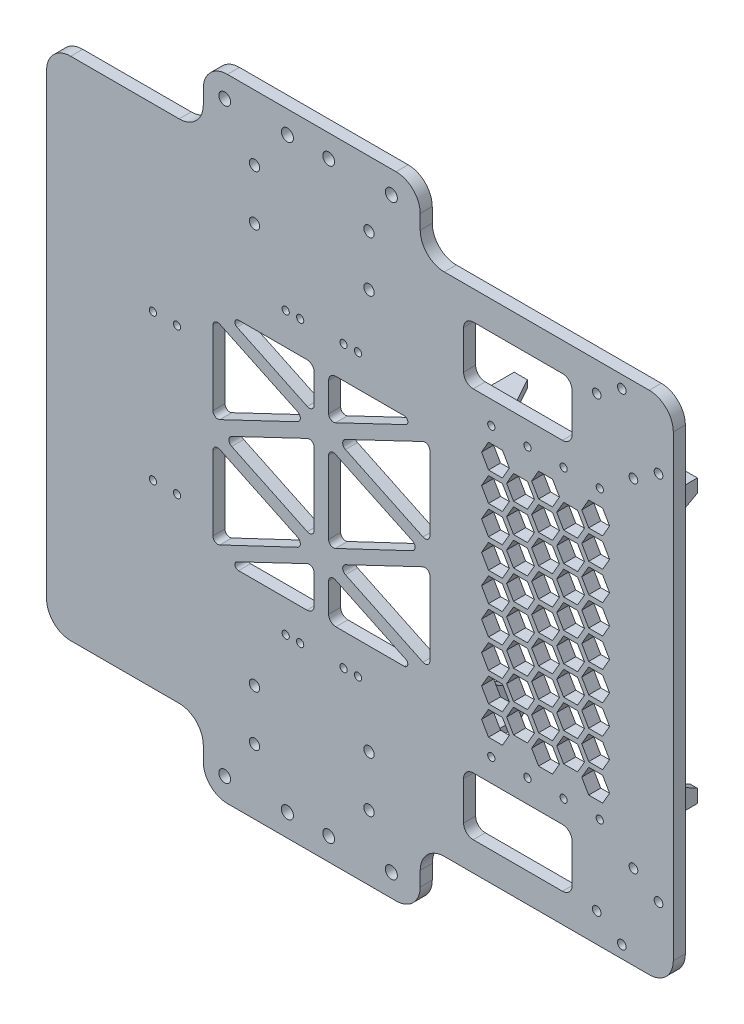
SolidWorks part; units mm, degrees
ref_plane "前视基准面" through (0, 0, 0) normal (0, 0, 1) x (1, 0, 0)
ref_plane "上视基准面" through (0, 0, 0) normal (0, 1, 0) x (1, 0, 0)
ref_plane "右视基准面" through (0, 0, 0) normal (1, 0, 0) x (0, 0, -1)
sketch "草图1" plane through (0, 0, 0) normal (0, 0, 1) x (1, 0, 0)
  line L2 (-130, 95) -> (-130, -95)
  line L3 (-120, -105) -> (-75, -105)
  line L4 (130, 95) -> (130, -95)
  line L5 (126.7518, 102.3765) -> (130, 105) construction
  line L6 (-130, -105) -> (-126.7518, -102.3765) construction
  line L9 (-65, -115) -> (-65, -121)
  line L10 (-55, -131) -> (15, -131)
  line L11 (25, -121) -> (25, -115)
  line L13 (35, -105) -> (120, -105)
  line L14 (126.7518, -102.3765) -> (130, -105) construction
  line L15 (-130, 105) -> (-126.7518, 102.3765) construction
  line L16 (-130, 0) -> (130, 0) construction
  line L17 (35, 105) -> (120, 105)
  line L18 (25, 121) -> (25, 115)
  line L19 (-55, 131) -> (15, 131)
  line L20 (-65, 115) -> (-65, 121)
  line L21 (-120, 105) -> (-75, 105)
  arc A1 (-120, -105) -> (-130, -95) centre (-120, -95) cw
  arc A3 (120, -105) -> (130, -95) centre (120, -95) ccw
  arc A8 (-65, -115) -> (-75, -105) centre (-75, -115) ccw
  arc A9 (25, -115) -> (35, -105) centre (35, -115) cw
  arc A10 (-55, -131) -> (-65, -121) centre (-55, -121) cw
  arc A11 (15, -131) -> (25, -121) centre (15, -121) ccw
  arc A12 (15, 131) -> (25, 121) centre (15, 121) cw
  arc A13 (-55, 131) -> (-65, 121) centre (-55, 121) ccw
  arc A14 (25, 115) -> (35, 105) centre (35, 115) ccw
  arc A15 (-65, 115) -> (-75, 105) centre (-75, 115) cw
  arc A16 (120, 105) -> (130, 95) centre (120, 95) cw
  arc A17 (-120, 105) -> (-130, 95) centre (-120, 95) ccw
  point P0 (0, 0)
  point P40 (25, -105)
  point P45 (25, 105)
  dimension "D2" = 10
  dimension "D3" = 65
  dimension "D4" = 10
  dimension "D5" = 105
  dimension "D7" = 10
  dimension "D8" = 10
  dimension "D10" = 10
  dimension "D12" = 10
  dimension "D13" = 105
  dimension "D18" = 90
  dimension "D19" = 6
extrude "凸台-拉伸1" add sketch "草图1" along normal blind 5
sketch "草图4" plane through (0, 0, 0) normal (0, 0, -1) x (-1, 0, 0)
  line L0 (-39, -47.5) -> (-39, -58.5)
  line L1 (-39, -58.5) -> (-50, -58.5)
  line L2 (-50, -58.5) -> (-50, -55.5)
  line L3 (-50, -55.5) -> (-42, -55.5)
  line L4 (-42, -55.5) -> (-42, -47.5)
  line L5 (-42, -47.5) -> (-39, -47.5)
  line L6 (-130, 0) -> (-25.5592, 0) construction
  line L7 (-130, -95) -> (-130, 95) construction
  line L10 (-130, -95) -> (-130, 95) construction
  dimension "D1" = 11
  dimension "D2" = 11
  dimension "D3" = 3
  dimension "D4" = 3
  dimension "D5" = 80
  dimension "D7" = 55.5
extrude "凸台-拉伸2" add sketch "草图4" along normal blind 20
sketch "草图5" plane through (0, -58.5, 0) normal (0, -1, 0) x (1, 0, 0)
  line L0 (50, -10) -> (44.5, -20)
  line L1 (50, -20) -> (50, 0) construction
  line L2 (50, -20) -> (39, -20) construction
  line L3 (44.5, -20) -> (50, -20)
  line L4 (50, -20) -> (50, -10)
  dimension "D1" = 10
  dimension "D2" = 5.5
extrude "切除-拉伸3" cut sketch "草图5" against normal blind 10
sketch "草图6" plane through (39, 0, 0) normal (-1, 0, 0) x (0, 0, 1)
  line L0 (-20, -53) -> (-10, -47.5)
  line L1 (-20, -58.5) -> (-20, -47.5) construction
  line L2 (-20, -47.5) -> (0, -47.5) construction
  line L3 (-10, -47.5) -> (-20, -47.5)
  line L4 (-20, -47.5) -> (-20, -53)
  dimension "D1" = 10
  dimension "D2" = 5.5
extrude "切除-拉伸4" cut sketch "草图6" against normal blind 10
ref_plane "基准面2" through (77, 0, 0) normal (1, 0, 0) x (0, 0, -1)
mirror "镜向1" about plane through (77, 0, 0) normal (1, 0, 0) of "凸台-拉伸2", "切除-拉伸4", "切除-拉伸3"
mirror "镜向2" about plane through (0, 0, 0) normal (0, 1, 0) of "镜向1"
sketch "草图7" plane through (0, 0, 0) normal (0, 0, -1) x (-1, 0, 0)
  line L4 (-112, -55.5) -> (-104, -55.5) construction
  line L5 (-112, 47.5) -> (-112, 55.5) construction
  line L6 (-112, 55.5) -> (-104, 55.5) construction
  line L7 (-92.013, 36) -> (-94.8997, 41)
  line L8 (-94.8997, 41) -> (-100.6732, 41)
  line L9 (-100.6732, 41) -> (-103.56, 36)
  line L10 (-103.56, 36) -> (-100.6732, 31)
  line L11 (-100.6732, 31) -> (-94.8997, 31)
  line L12 (-94.8997, 31) -> (-92.013, 36)
  line L13 (-77.0019, 36) -> (-97.7865, 36) construction
  line L14 (-74.1151, 31) -> (-71.2284, 36)
  line L15 (-71.2284, 36) -> (-74.1151, 41)
  line L16 (-74.1151, 41) -> (-79.8886, 41)
  line L17 (-79.8886, 41) -> (-82.7754, 36)
  line L18 (-82.7754, 36) -> (-79.8886, 31)
  line L19 (-79.8886, 31) -> (-74.1151, 31)
  line L20 (-92.013, 24) -> (-94.8997, 29)
  line L21 (-93.1677, 30) -> (-90.2809, 25)
  line L22 (-90.2809, 25) -> (-84.5074, 25)
  line L23 (-84.5074, 25) -> (-81.6207, 30)
  line L24 (-81.6207, 30) -> (-84.5074, 35)
  line L25 (-84.5074, 35) -> (-90.2809, 35)
  line L26 (-90.2809, 35) -> (-93.1677, 30)
  line L27 (-84.5074, 37) -> (-81.6207, 42)
  line L28 (-81.6207, 42) -> (-84.5074, 47)
  line L29 (-84.5074, 47) -> (-90.2809, 47)
  line L30 (-90.2809, 47) -> (-93.1677, 42)
  line L31 (-93.1677, 42) -> (-90.2809, 37)
  line L32 (-90.2809, 37) -> (-84.5074, 37)
  line L33 (-79.8886, 43) -> (-74.1151, 43)
  line L34 (-74.1151, 43) -> (-71.2284, 48)
  line L35 (-71.2284, 48) -> (-74.1151, 53)
  line L36 (-74.1151, 53) -> (-79.8886, 53)
  line L37 (-79.8886, 53) -> (-82.7754, 48)
  line L38 (-82.7754, 48) -> (-79.8886, 43)
  line L39 (-94.8997, 43) -> (-92.013, 48)
  line L40 (-92.013, 48) -> (-94.8997, 53)
  line L41 (-94.8997, 53) -> (-100.6732, 53)
  line L42 (-100.6732, 53) -> (-103.56, 48)
  line L43 (-103.56, 48) -> (-100.6732, 43)
  line L44 (-100.6732, 43) -> (-94.8997, 43)
  line L45 (-72.3831, 42) -> (-69.4963, 37)
  line L46 (-69.4963, 37) -> (-63.7228, 37)
  line L47 (-63.7228, 37) -> (-60.8361, 42)
  line L48 (-60.8361, 42) -> (-63.7228, 47)
  line L49 (-63.7228, 47) -> (-69.4963, 47)
  line L50 (-69.4963, 47) -> (-72.3831, 42)
  line L51 (-94.8997, 29) -> (-100.6732, 29)
  line L52 (-100.6732, 29) -> (-103.56, 24)
  line L53 (-103.56, 24) -> (-100.6732, 19)
  line L54 (-100.6732, 19) -> (-94.8997, 19)
  line L55 (-94.8997, 19) -> (-92.013, 24)
  line L56 (-93.1677, 18) -> (-90.2809, 13)
  line L57 (-90.2809, 13) -> (-84.5074, 13)
  line L58 (-84.5074, 13) -> (-81.6207, 18)
  line L59 (-81.6207, 18) -> (-84.5074, 23)
  line L60 (-84.5074, 23) -> (-90.2809, 23)
  line L61 (-90.2809, 23) -> (-93.1677, 18)
  line L62 (-74.1151, 19) -> (-71.2284, 24)
  line L63 (-71.2284, 24) -> (-74.1151, 29)
  line L64 (-74.1151, 29) -> (-79.8886, 29)
  line L65 (-79.8886, 29) -> (-82.7754, 24)
  line L66 (-82.7754, 24) -> (-79.8886, 19)
  line L67 (-79.8886, 19) -> (-74.1151, 19)
  line L68 (-72.3831, 30) -> (-69.4963, 25)
  line L69 (-69.4963, 25) -> (-63.7228, 25)
  line L70 (-63.7228, 25) -> (-60.8361, 30)
  line L71 (-60.8361, 30) -> (-63.7228, 35)
  line L72 (-63.7228, 35) -> (-69.4963, 35)
  line L73 (-69.4963, 35) -> (-72.3831, 30)
  line L74 (-92.013, 12) -> (-94.8997, 17)
  line L75 (-94.8997, 17) -> (-100.6732, 17)
  line L76 (-100.6732, 17) -> (-103.56, 12)
  line L77 (-103.56, 12) -> (-100.6732, 7)
  line L78 (-100.6732, 7) -> (-94.8997, 7)
  line L79 (-94.8997, 7) -> (-92.013, 12)
  line L80 (-93.1677, 6) -> (-90.2809, 1)
  line L81 (-90.2809, 1) -> (-84.5074, 1)
  line L82 (-84.5074, 1) -> (-81.6207, 6)
  line L83 (-81.6207, 6) -> (-84.5074, 11)
  line L84 (-84.5074, 11) -> (-90.2809, 11)
  line L85 (-90.2809, 11) -> (-93.1677, 6)
  line L86 (-74.1151, 7) -> (-71.2284, 12)
  line L87 (-71.2284, 12) -> (-74.1151, 17)
  line L88 (-74.1151, 17) -> (-79.8886, 17)
  line L89 (-79.8886, 17) -> (-82.7754, 12)
  line L90 (-82.7754, 12) -> (-79.8886, 7)
  line L91 (-79.8886, 7) -> (-74.1151, 7)
  line L92 (-72.3831, 18) -> (-69.4963, 13)
  line L93 (-69.4963, 13) -> (-63.7228, 13)
  line L94 (-63.7228, 13) -> (-60.8361, 18)
  line L95 (-60.8361, 18) -> (-63.7228, 23)
  line L96 (-63.7228, 23) -> (-69.4963, 23)
  line L97 (-69.4963, 23) -> (-72.3831, 18)
  line L98 (-92.013, 0) -> (-94.8997, 5)
  line L99 (-94.8997, 5) -> (-100.6732, 5)
  line L100 (-100.6732, 5) -> (-103.56, 0)
  line L101 (-103.56, 0) -> (-100.6732, -5)
  line L102 (-100.6732, -5) -> (-94.8997, -5)
  line L103 (-94.8997, -5) -> (-92.013, 0)
  line L104 (-93.1677, -6) -> (-90.2809, -11)
  line L105 (-90.2809, -11) -> (-84.5074, -11)
  line L106 (-84.5074, -11) -> (-81.6207, -6)
  line L107 (-81.6207, -6) -> (-84.5074, -1)
  line L108 (-84.5074, -1) -> (-90.2809, -1)
  line L109 (-90.2809, -1) -> (-93.1677, -6)
  line L110 (-74.1151, -5) -> (-71.2284, 0)
  line L111 (-71.2284, 0) -> (-74.1151, 5)
  line L112 (-74.1151, 5) -> (-79.8886, 5)
  line L113 (-79.8886, 5) -> (-82.7754, 0)
  line L114 (-82.7754, 0) -> (-79.8886, -5)
  line L115 (-79.8886, -5) -> (-74.1151, -5)
  line L116 (-72.3831, 6) -> (-69.4963, 1)
  line L117 (-69.4963, 1) -> (-63.7228, 1)
  line L118 (-63.7228, 1) -> (-60.8361, 6)
  line L119 (-60.8361, 6) -> (-63.7228, 11)
  line L120 (-63.7228, 11) -> (-69.4963, 11)
  line L121 (-69.4963, 11) -> (-72.3831, 6)
  line L122 (-92.013, -12) -> (-94.8997, -7)
  line L123 (-94.8997, -7) -> (-100.6732, -7)
  line L124 (-100.6732, -7) -> (-103.56, -12)
  line L125 (-103.56, -12) -> (-100.6732, -17)
  line L126 (-100.6732, -17) -> (-94.8997, -17)
  line L127 (-94.8997, -17) -> (-92.013, -12)
  line L128 (-93.1677, -18) -> (-90.2809, -23)
  line L129 (-90.2809, -23) -> (-84.5074, -23)
  line L130 (-84.5074, -23) -> (-81.6207, -18)
  line L131 (-81.6207, -18) -> (-84.5074, -13)
  line L132 (-84.5074, -13) -> (-90.2809, -13)
  line L133 (-90.2809, -13) -> (-93.1677, -18)
  line L134 (-74.1151, -17) -> (-71.2284, -12)
  line L135 (-71.2284, -12) -> (-74.1151, -7)
  line L136 (-74.1151, -7) -> (-79.8886, -7)
  line L137 (-79.8886, -7) -> (-82.7754, -12)
  line L138 (-82.7754, -12) -> (-79.8886, -17)
  line L139 (-79.8886, -17) -> (-74.1151, -17)
  line L140 (-72.3831, -6) -> (-69.4963, -11)
  line L141 (-69.4963, -11) -> (-63.7228, -11)
  line L142 (-63.7228, -11) -> (-60.8361, -6)
  line L143 (-60.8361, -6) -> (-63.7228, -1)
  line L144 (-63.7228, -1) -> (-69.4963, -1)
  line L145 (-69.4963, -1) -> (-72.3831, -6)
  line L146 (-92.013, -24) -> (-94.8997, -19)
  line L147 (-94.8997, -19) -> (-100.6732, -19)
  line L148 (-100.6732, -19) -> (-103.56, -24)
  line L149 (-103.56, -24) -> (-100.6732, -29)
  line L150 (-100.6732, -29) -> (-94.8997, -29)
  line L151 (-94.8997, -29) -> (-92.013, -24)
  line L152 (-93.1677, -30) -> (-90.2809, -35)
  line L153 (-90.2809, -35) -> (-84.5074, -35)
  line L154 (-84.5074, -35) -> (-81.6207, -30)
  line L155 (-81.6207, -30) -> (-84.5074, -25)
  line L156 (-84.5074, -25) -> (-90.2809, -25)
  line L157 (-90.2809, -25) -> (-93.1677, -30)
  line L158 (-74.1151, -29) -> (-71.2284, -24)
  line L159 (-71.2284, -24) -> (-74.1151, -19)
  line L160 (-74.1151, -19) -> (-79.8886, -19)
  line L161 (-79.8886, -19) -> (-82.7754, -24)
  line L162 (-82.7754, -24) -> (-79.8886, -29)
  line L163 (-79.8886, -29) -> (-74.1151, -29)
  line L164 (-72.3831, -18) -> (-69.4963, -23)
  line L165 (-69.4963, -23) -> (-63.7228, -23)
  line L166 (-63.7228, -23) -> (-60.8361, -18)
  line L167 (-60.8361, -18) -> (-63.7228, -13)
  line L168 (-63.7228, -13) -> (-69.4963, -13)
  line L169 (-69.4963, -13) -> (-72.3831, -18)
  line L170 (-92.013, -36) -> (-94.8997, -31)
  line L171 (-94.8997, -31) -> (-100.6732, -31)
  line L172 (-100.6732, -31) -> (-103.56, -36)
  line L173 (-103.56, -36) -> (-100.6732, -41)
  line L174 (-100.6732, -41) -> (-94.8997, -41)
  line L175 (-94.8997, -41) -> (-92.013, -36)
  line L176 (-93.1677, -42) -> (-90.2809, -47)
  line L177 (-90.2809, -47) -> (-84.5074, -47)
  line L178 (-84.5074, -47) -> (-81.6207, -42)
  line L179 (-81.6207, -42) -> (-84.5074, -37)
  line L180 (-84.5074, -37) -> (-90.2809, -37)
  line L181 (-90.2809, -37) -> (-93.1677, -42)
  line L182 (-74.1151, -41) -> (-71.2284, -36)
  line L183 (-71.2284, -36) -> (-74.1151, -31)
  line L184 (-74.1151, -31) -> (-79.8886, -31)
  line L185 (-79.8886, -31) -> (-82.7754, -36)
  line L186 (-82.7754, -36) -> (-79.8886, -41)
  line L187 (-79.8886, -41) -> (-74.1151, -41)
  line L188 (-72.3831, -30) -> (-69.4963, -35)
  line L189 (-69.4963, -35) -> (-63.7228, -35)
  line L190 (-63.7228, -35) -> (-60.8361, -30)
  line L191 (-60.8361, -30) -> (-63.7228, -25)
  line L192 (-63.7228, -25) -> (-69.4963, -25)
  line L193 (-69.4963, -25) -> (-72.3831, -30)
  line L194 (-92.013, -48) -> (-94.8997, -43)
  line L195 (-94.8997, -43) -> (-100.6732, -43)
  line L196 (-100.6732, -43) -> (-103.56, -48)
  line L197 (-103.56, -48) -> (-100.6732, -53)
  line L198 (-100.6732, -53) -> (-94.8997, -53)
  line L199 (-94.8997, -53) -> (-92.013, -48)
  line L206 (-74.1151, -53) -> (-71.2284, -48)
  line L207 (-71.2284, -48) -> (-74.1151, -43)
  line L208 (-74.1151, -43) -> (-79.8886, -43)
  line L209 (-79.8886, -43) -> (-82.7754, -48)
  line L210 (-82.7754, -48) -> (-79.8886, -53)
  line L211 (-79.8886, -53) -> (-74.1151, -53)
  line L212 (-72.3831, -42) -> (-69.4963, -47)
  line L213 (-69.4963, -47) -> (-63.7228, -47)
  line L214 (-63.7228, -47) -> (-60.8361, -42)
  line L215 (-60.8361, -42) -> (-63.7228, -37)
  line L216 (-63.7228, -37) -> (-69.4963, -37)
  line L217 (-69.4963, -37) -> (-72.3831, -42)
  line L218 (-61.9908, 36) -> (-59.104, 31)
  line L219 (-61.9908, 48) -> (-59.104, 43)
  line L220 (-59.104, 43) -> (-53.3305, 43)
  line L221 (-53.3305, 43) -> (-50.4438, 48)
  line L222 (-50.4438, 48) -> (-53.3305, 53)
  line L223 (-53.3305, 53) -> (-59.104, 53)
  line L224 (-59.104, 53) -> (-61.9908, 48)
  line L225 (-59.104, 31) -> (-53.3305, 31)
  line L226 (-53.3305, 31) -> (-50.4438, 36)
  line L227 (-50.4438, 36) -> (-53.3305, 41)
  line L228 (-53.3305, 41) -> (-59.104, 41)
  line L229 (-59.104, 41) -> (-61.9908, 36)
  line L230 (-61.9908, 24) -> (-59.104, 19)
  line L231 (-59.104, 19) -> (-53.3305, 19)
  line L232 (-53.3305, 19) -> (-50.4438, 24)
  line L233 (-50.4438, 24) -> (-53.3305, 29)
  line L234 (-53.3305, 29) -> (-59.104, 29)
  line L235 (-59.104, 29) -> (-61.9908, 24)
  line L236 (-61.9908, 12) -> (-59.104, 7)
  line L237 (-59.104, 7) -> (-53.3305, 7)
  line L238 (-53.3305, 7) -> (-50.4438, 12)
  line L239 (-50.4438, 12) -> (-53.3305, 17)
  line L240 (-53.3305, 17) -> (-59.104, 17)
  line L241 (-59.104, 17) -> (-61.9908, 12)
  line L242 (-61.9908, 0) -> (-59.104, -5)
  line L243 (-59.104, -5) -> (-53.3305, -5)
  line L244 (-53.3305, -5) -> (-50.4438, 0)
  line L245 (-50.4438, 0) -> (-53.3305, 5)
  line L246 (-53.3305, 5) -> (-59.104, 5)
  line L247 (-59.104, 5) -> (-61.9908, 0)
  line L248 (-61.9908, -12) -> (-59.104, -17)
  line L249 (-59.104, -17) -> (-53.3305, -17)
  line L250 (-53.3305, -17) -> (-50.4438, -12)
  line L251 (-50.4438, -12) -> (-53.3305, -7)
  line L252 (-53.3305, -7) -> (-59.104, -7)
  line L253 (-59.104, -7) -> (-61.9908, -12)
  line L254 (-61.9908, -24) -> (-59.104, -29)
  line L255 (-59.104, -29) -> (-53.3305, -29)
  line L256 (-53.3305, -29) -> (-50.4438, -24)
  line L257 (-50.4438, -24) -> (-53.3305, -19)
  line L258 (-53.3305, -19) -> (-59.104, -19)
  line L259 (-59.104, -19) -> (-61.9908, -24)
  line L260 (-61.9908, -36) -> (-59.104, -41)
  line L261 (-59.104, -41) -> (-53.3305, -41)
  line L262 (-53.3305, -41) -> (-50.4438, -36)
  line L263 (-50.4438, -36) -> (-53.3305, -31)
  line L264 (-53.3305, -31) -> (-59.104, -31)
  line L265 (-59.104, -31) -> (-61.9908, -36)
  line L266 (-61.9908, -48) -> (-59.104, -53)
  line L267 (-59.104, -53) -> (-53.3305, -53)
  line L268 (-53.3305, -53) -> (-50.4438, -48)
  line L269 (-50.4438, -48) -> (-53.3305, -43)
  line L270 (-53.3305, -43) -> (-59.104, -43)
  line L271 (-59.104, -43) -> (-61.9908, -48)
  line L272 (-93.1677, -54) -> (-90.2809, -59) [skipped]
  line L273 (-90.2809, -59) -> (-84.5074, -59) [skipped]
  line L274 (-84.5074, -59) -> (-81.6207, -54) [skipped]
  line L275 (-81.6207, -54) -> (-84.5074, -49) [skipped]
  line L276 (-84.5074, -49) -> (-90.2809, -49) [skipped]
  line L277 (-90.2809, -49) -> (-93.1677, -54) [skipped]
  circle A0 centre (-97.7865, 36) radius 5 construction
  circle A1 centre (-77.0019, 36) radius 5 construction
  circle A2 centre (-87.3942, 30) radius 5 construction
  circle A3 centre (-87.3942, 42) radius 5 construction
  circle A4 centre (-77.0019, 48) radius 5 construction
  circle A5 centre (-97.7865, 48) radius 5 construction
  circle A6 centre (-66.6096, 42) radius 5 construction
  circle A7 centre (-56.2173, 48) radius 5 construction
  point P4 (-87.3942, 37)
  dimension "D1" = 2
  dimension "D3" = 10
  dimension "D4" = 10
  dimension "D5" = 2
  dimension "D7" = 10
  dimension "D11" = 10
  dimension "D14" = 10
  dimension "D15" = 10
  dimension "D20" = 10
  dimension "D2" = 2
  dimension "D6" = 2
  dimension "D8" = 2
  dimension "D9" = 2
  dimension "D10" = 2
  dimension "D12" = 2
  dimension "D13" = 2
  dimension "D16" = 2
  dimension "D17" = 2
  dimension "D19" = 2
  dimension "D21" = 9
  dimension "D22" = 2.5
  dimension "D23" = 2.5
  dimension "D24" = 8.44
  dimension "D18" = 8
extrude "切除-拉伸5" cut sketch "草图7" against normal blind 5
sketch "草图8" plane through (0, 0, 0) normal (0, 0, -1) x (-1, 0, 0)
  line L0 (-75.3677, 120) -> (-75.3677, -120)
  line L1 (-100.0285, 77.2863) -> (-100.0285, -77.2863)
  line L2 (-100.0285, 77.2863) -> (-75.3677, 120)
  line L3 (-100.0285, -77.2863) -> (-75.3677, -120)
  line L4 (-37.1297, 0) -> (-146.8562, 0) construction
  dimension "D1" = 30
  dimension "D2" = 30
  dimension "D3" = 120
  dimension "D4" = 120
sketch "草图9" plane through (0, 0, 0) normal (0, 0, -1) x (-1, 0, 0)
  line L0 (148.8518, 0) -> (-37.1297, 0) construction
  line L1 (-29, 41) -> (-29, 4)
  line L2 (-25, -45) -> (13, -45)
  line L3 (61, -41) -> (61, -4)
  line L4 (57, 45) -> (19, 45)
  line L14 (-29, 41) -> (9.8049, 22.5)
  line L15 (57, 0) -> (19, -18.1163)
  line L16 (130, 95) -> (130, -95) construction
  line L17 (63, 93) -> (118, 93)
  line L18 (63, 93) -> (63, 66)
  line L19 (63, 66) -> (118, 66)
  line L20 (118, 93) -> (118, 66)
  line L21 (75, 105) -> (120, 105) construction
  line L22 (63, -66) -> (118, -66)
  line L23 (118, -93) -> (118, -66)
  line L24 (63, -93) -> (118, -93)
  line L25 (63, -93) -> (63, -66)
  line L26 (-120, 105) -> (-35, 105) construction
  line L27 (-43, 93) -> (-88, 93)
  line L28 (-43, 93) -> (-43, 69)
  line L29 (-43, 69) -> (-88, 69)
  line L30 (-88, 93) -> (-88, 69)
  line L31 (-130, -95) -> (-130, 95) construction
  line L32 (-43, -69) -> (-88, -69)
  line L33 (-88, -93) -> (-88, -69)
  line L34 (-43, -93) -> (-88, -93)
  line L35 (-43, -93) -> (-43, -69)
  line L36 (-25, 45) -> (13, 26.8837)
  line L37 (-25, -45) -> (13, -26.8837)
  line L38 (61, 41) -> (22.0746, 22.5575)
  line L39 (-25.5359, 0) -> (13, -18.258)
  line L40 (57, 45) -> (19, 26.8837)
  line L41 (57, -45) -> (19, -26.8837)
  line L42 (16, 61.4977) -> (16, -60.5731) construction
  line L43 (13, 45) -> (13, 26.8837)
  line L44 (19, 45) -> (19, 26.8837)
  line L45 (13, 18.258) -> (13, -18.258)
  line L46 (9.8049, 22.5) -> (-29, 4)
  line L47 (19, 18.1163) -> (57, 0)
  line L48 (22.0746, 22.5575) -> (61, 4)
  line L49 (13, 18.258) -> (-25.5359, 0)
  line L50 (19, 18.1163) -> (19, -18.1163)
  line L51 (22.0746, -22.5575) -> (61, -41)
  line L52 (9.8049, -22.5) -> (-29, -41)
  line L53 (9.8049, -22.5) -> (-29, -4)
  line L54 (22.0746, -22.5575) -> (61, -4)
  line L55 (13, -26.8837) -> (13, -45)
  line L56 (19, -26.8837) -> (19, -45)
  line L57 (13, 45) -> (-25, 45)
  line L58 (-29, -4) -> (-29, -41)
  line L59 (19, -45) -> (57, -45)
  line L60 (61, 4) -> (61, 41)
  line L61 (-44, 41) -> (-44, -37.8122) construction
  dimension "D1" = 45
  dimension "D2" = 45
  dimension "D3" = 15
  dimension "D4" = 90
  dimension "D5" = 1
  dimension "D7" = 12
  dimension "D8" = 12
  dimension "D9" = 27
  dimension "D10" = 55
  dimension "D11" = 12
  dimension "D12" = 45
  dimension "D13" = 42
  dimension "D14" = 24
  dimension "D21" = 4
  dimension "D22" = 4
  dimension "D23" = 4
  dimension "D24" = 4
  dimension "D26" = 4
  dimension "D27" = 3
  dimension "D28" = 45
extrude "切除-拉伸6" cut sketch "草图9" against normal blind 5 contours L27 L30 L29 L28 | L34 L35 L32 L33 | L4 L44 L40 | L48 L60 L38 | L47 L50 L15 | L54 L51 L3 | L56 L59 L41 | L55 L37 L2 | L53 L58 L52 | L45 L49 L39 | L46 L14 L1 | L43 L57 L36 | L57 L36 L43 region at (16.065, 22.5, 0) region at (-0.3333, -38.9612, 0) region at (-48.0249, -22.5192, 0) region at (-31.6667, 38.9612, 0) region at (-31.6667, 0, 0) region at (65.5, 81, 0) region at (65.5, -81, 0) region at (-0.3333, 38.9612, 0) region at (-48.0249, 22.5192, 0) region at (-0.1547, 0, 0) region at (-31.6667, -38.9612, 0) region at (16.065, -22.5, 0)
fillet "圆角1" radius 4 8 edges at (43, -93, 2.5) (88, -69, 2.5) (43, -69, 2.5) (88, -93, 2.5) (88, 69, 2.5) (43, 69, 2.5) (43, 93, 2.5) (88, 93, 2.5)
fillet "圆角2" radius 1.5 4 edges at (25, -45, 2.5) (-57, -45, 2.5) (25, 45, 2.5) (-57, 45, 2.5)
fillet "圆角3" radius 2 22 edges at (29, -4, 2.5) (29, 4, 2.5) (-13, -18.258, 2.5) (-61, -41, 2.5) (-61, 4, 2.5) (-13, -26.8837, 2.5) (-13, 18.258, 2.5) (-61, -4, 2.5) (-22.0746, -22.5575, 2.5) (25.5359, 0, 2.5) (-22.0746, 22.5575, 2.5) (-61, 41, 2.5) (-19, 26.8837, 2.5) (-19, -26.8837, 2.5) (-19, -18.1163, 2.5) (29, -41, 2.5) (29, 41, 2.5) (-57, 0, 2.5) (-9.8049, -22.5, 2.5) (-13, 26.8837, 2.5) (-9.8049, 22.5, 2.5) (-19, 18.1163, 2.5)
fillet "圆角4" radius 3 4 edges at (-13, -45, 2.5) (-13, 45, 2.5) (-19, -45, 2.5) (-19, 45, 2.5)
sketch "草图10" plane through (0, 0, 0) normal (0, 0, -1) x (-1, 0, 0)
  line L0 (-37.1297, 0) -> (-146.8562, 0) construction
  line L1 (-37.1297, 0) -> (-146.8562, 0) construction
  circle A0 centre (-123.8743, 76.9597) radius 1.8 construction
  circle A1 centre (-113.4687, 70.0334) radius 1.8 construction
  circle A2 centre (-108.6364, 99.852) radius 1.8 construction
  circle A3 centre (-98.2308, 92.9256) radius 1.8 construction
  circle A4 centre (-3.75, 104) radius 2.15 construction
  circle A5 centre (-3.75, 104) radius 2.15
  circle A6 centre (-3.75, -104) radius 2.15
  circle A11 centre (-13.0267, 121.679) radius 2.5 construction
  circle A12 centre (56.0941, 121.679) radius 2.45 construction
  circle A13 centre (30.0941, 121.679) radius 2.5 construction
  circle A14 centre (12.9733, 121.679) radius 2.45 construction
  circle A15 centre (-123.8743, 76.9597) radius 1.8
  circle A16 centre (-113.4687, 70.0334) radius 1.8
  circle A17 centre (-108.6364, 99.852) radius 1.8
  circle A18 centre (-98.2308, 92.9256) radius 1.8
  circle A26 centre (-13.0267, 121.679) radius 2.5
  circle A27 centre (56.0941, 121.679) radius 2.45
  circle A28 centre (30.0941, 121.679) radius 2.5
  circle A29 centre (12.9733, 121.679) radius 2.45
  circle A30 centre (12.9733, -121.679) radius 2.45
  circle A31 centre (30.0941, -121.679) radius 2.5
  circle A32 centre (56.0941, -121.679) radius 2.45
  circle A33 centre (-13.0267, -121.679) radius 2.5
  circle A41 centre (-98.2308, -92.9256) radius 1.8
  circle A42 centre (-108.6364, -99.852) radius 1.8
  circle A43 centre (-113.4687, -70.0334) radius 1.8
  circle A44 centre (-123.8743, -76.9597) radius 1.8
  circle A45 centre (-99.5, 59.5) radius 1.5 construction
  circle A46 centre (-84.5, 59.5) radius 1.5 construction
  circle A47 centre (-69.5, 59.5) radius 1.5 construction
  circle A48 centre (-54.5, 59.5) radius 1.5 construction
  circle A49 centre (0.8061, 58.25) radius 1.5 construction
  circle A50 centre (6.8061, 58.25) radius 1.5 construction
  circle A51 centre (24.8061, 58.25) radius 1.5 construction
  circle A52 centre (30.8061, 58.25) radius 1.5 construction
  circle A53 centre (-99.5, 59.5) radius 1.5
  circle A54 centre (-84.5, 59.5) radius 1.5
  circle A55 centre (-69.5, 59.5) radius 1.5
  circle A56 centre (-54.5, 59.5) radius 1.5
  circle A57 centre (0.8061, 58.25) radius 1.5
  circle A58 centre (6.8061, 58.25) radius 1.5
  circle A59 centre (24.8061, 58.25) radius 1.5
  circle A60 centre (30.8061, 58.25) radius 1.5
  circle A61 centre (30.8061, -58.25) radius 1.5
  circle A62 centre (24.8061, -58.25) radius 1.5
  circle A63 centre (6.8061, -58.25) radius 1.5
  circle A64 centre (0.8061, -58.25) radius 1.5
  circle A65 centre (-54.5, -59.5) radius 1.5
  circle A66 centre (-69.5, -59.5) radius 1.5
  circle A67 centre (-84.5, -59.5) radius 1.5
  circle A68 centre (-99.5, -59.5) radius 1.5
  circle A89 centre (75.897, 30.3) radius 1.5 construction
  circle A90 centre (85.897, 30.3) radius 1.5 construction
  circle A91 centre (75.897, 30.3) radius 1.5
  circle A92 centre (85.897, 30.3) radius 1.5
  circle A93 centre (85.897, -30.3) radius 1.5
  circle A94 centre (75.897, -30.3) radius 1.5
  circle A95 centre (43.75, 83) radius 2.15 construction
  circle A96 centre (43.75, 104) radius 2.15 construction
  circle A97 centre (-3.75, 83) radius 2.15 construction
  circle A99 centre (43.75, 83) radius 2.15
  circle A100 centre (43.75, 104) radius 2.15
  circle A101 centre (-3.75, 83) radius 2.15
  circle A104 centre (-3.75, -83) radius 2.15
  circle A105 centre (43.75, -104) radius 2.15
  circle A106 centre (43.75, -83) radius 2.15
  point P18 (-3.75, 104)
extrude "切除-拉伸7" cut sketch "草图10" against normal through all
equation "\"45、\"=43.7672"
